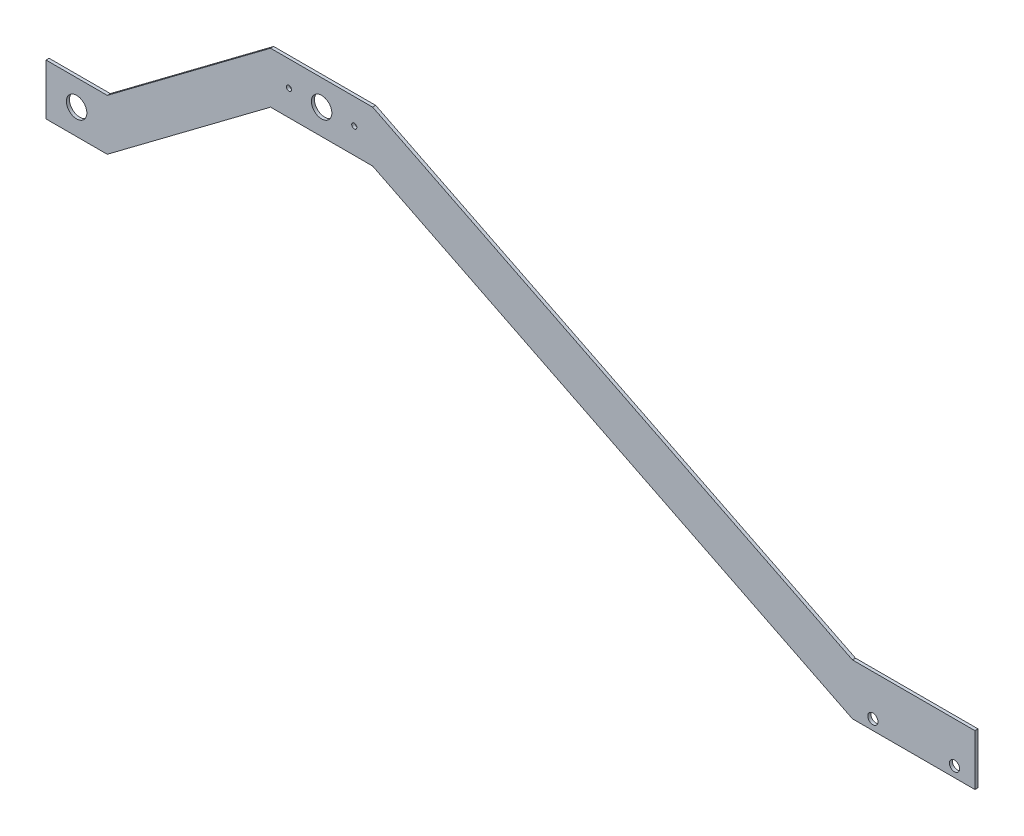
SolidWorks part; units mm, degrees
ref_plane "Front Plane" through (0, 0, 0) normal (0, 0, 1) x (1, 0, 0)
ref_plane "Top Plane" through (0, 0, 0) normal (0, 1, 0) x (1, 0, 0)
ref_plane "Right Plane" through (0, 0, 0) normal (1, 0, 0) x (0, 0, -1)
sketch "Sketch1" plane through (0, 0, 0) normal (0, 0, 1) x (1, 0, 0)
  line L0 (-60, 25) -> (-530, 258.9338)
  line L1 (-60, 25) -> (60, 25)
  line L3 (-60, -25) -> (60, -25)
  line L4 (60, 25) -> (60, -25)
  line L5 (-60, 25) -> (60, -25) construction
  line L6 (-60, -25) -> (60, 25) construction
  line L7 (-60, -25) -> (-530, 208.9338)
  line L8 (-530, 258.9338) -> (-630, 258.9338)
  line L10 (-630, 208.9338) -> (-530, 208.9338)
  line L11 (-630, 208.9338) -> (-790, 88.9338)
  line L12 (-630, 258.9338) -> (-790, 138.9338)
  line L13 (-790, 138.9338) -> (-850, 138.9338)
  line L14 (-850, 138.9338) -> (-850, 88.9338)
  line L15 (-850, 88.9338) -> (-790, 88.9338)
  line L16 (-790, 138.9338) -> (-790, 88.9338)
  point P0 (0, 0)
  dimension "D1" = 120
  dimension "D2" = 50
  dimension "D3" = 525
  dimension "D4" = 100
  dimension "D5" = 50
  dimension "D6" = 470
  dimension "D7" = 200
  dimension "D8" = 60
  dimension "D9" = 160
extrude "Boss-Extrude3" add sketch "Sketch1" along normal blind 3 contours L12 L16 L11 L10 L7 L3 L4 L1 L0 L8 | L16 L13 L14 L15 region at (0, 16.0383, 0) region at (-820, 113.9338, 0)
sketch "Sketch3" plane through (0, 0, 3) normal (0, 0, 1) x (1, 0, 0)
  line L0 (-530, 258.9338) -> (-630, 258.9338) construction
  line L1 (-850, 138.9338) -> (-850, 88.9338) construction
  line L2 (-790, 138.9338) -> (-850, 138.9338) construction
  line L3 (60, 25) -> (60, -25) construction
  line L4 (-60, -25) -> (60, -25) construction
  line L5 (-60, 25) -> (-530, 258.9338) construction
  line L6 (-60, -25) -> (-530, 208.9338) construction
  line L7 (-60, 25) -> (-60, -25)
  line L9 (-530, 258.9338) -> (-530, 145.5872)
  circle A0 centre (-580, 233.9338) radius 10
  circle A2 centre (-820, 113.9338) radius 10
  circle A3 centre (40, -15) radius 5
  circle A4 centre (-40, -15) radius 5
  dimension "D1" = 20
  dimension "D4" = 20
  dimension "D7" = 10
  dimension "D8" = 10
  dimension "D2" = 25
  dimension "D3" = 50
  dimension "D5" = 30
  dimension "D6" = 25
  dimension "D9" = 20
  dimension "D10" = 20
  dimension "D11" = 10
  dimension "D12" = 10
  dimension "D15" = 44.7619
extrude "Cut-Extrude1" cut sketch "Sketch3" against normal through all contours A2 | A0 | A4 | A3 region at (-580, 233.9338, 3) region at (-820, 113.9338, 3) region at (40, -15, 3) region at (-40, -15, 3)
sketch "Sketch4" plane through (0, 0, 3) normal (0, 0, 1) x (1, 0, 0)
  line L0 (-530, 258.9338) -> (-630, 258.9338) construction
  line L2 (-630, 208.9338) -> (-530, 208.9338) construction
  circle A0 centre (-548, 233.9338) radius 2.5
  circle A1 centre (-612, 233.9338) radius 2.5
  circle A3 centre (-580, 233.9338) radius 10 construction
  dimension "D1" = 5
  dimension "D2" = 5
  dimension "D3" = 32
  dimension "D4" = 32
  dimension "D5" = 25
  dimension "D6" = 25
extrude "Cut-Extrude2" cut sketch "Sketch4" against normal blind 10
